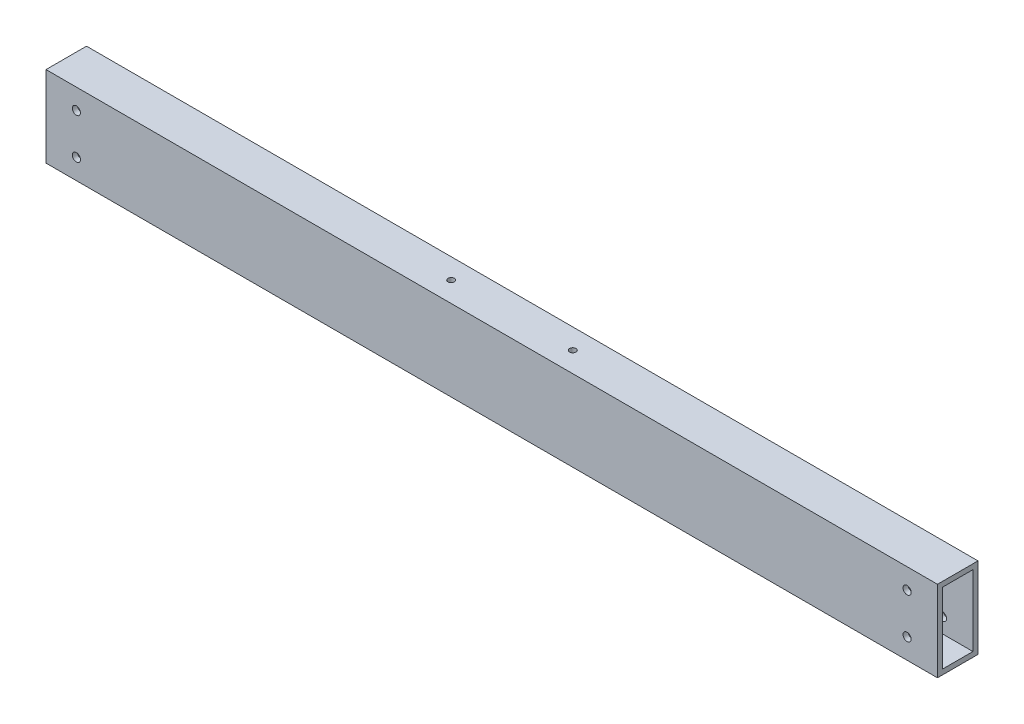
SolidWorks part; units mm, degrees
material "6061-T6 (SS)"
ref_plane "Front Plane" through (0, 0, 0) normal (0, 0, 1) x (1, 0, 0)
ref_plane "Top Plane" through (0, 0, 0) normal (0, 1, 0) x (1, 0, 0)
ref_plane "Right Plane" through (0, 0, 0) normal (1, 0, 0) x (0, 0, -1)
sketch "Sketch1" plane through (0, 0, 0) normal (0, 0, 1) x (1, 0, 0)
  line L1 (-279.4, 25.4) -> (279.4, 25.4)
  line L2 (-279.4, 25.4) -> (-279.4, -25.4)
  line L3 (-279.4, -25.4) -> (279.4, -25.4)
  line L4 (279.4, 25.4) -> (279.4, -25.4)
  line L5 (-279.4, 25.4) -> (279.4, -25.4) construction
  line L6 (-279.4, -25.4) -> (279.4, 25.4) construction
  point P0 (0, 0)
  dimension "D1" = 50.8
  dimension "D2" = 558.8
extrude "Boss-Extrude1" add sketch "Sketch1" along normal mid plane 25.4
sketch "Sketch2" plane through (279.4, 0, 0) normal (1, 0, 0) x (0, 0, -1)
  line L8 (9.525, -22.225) -> (9.525, 22.225)
  line L9 (9.525, 22.225) -> (-9.525, 22.225)
  line L10 (-9.525, 22.225) -> (-9.525, -22.225)
  line L11 (-9.525, -22.225) -> (9.525, -22.225)
  line L12 (9.525, -22.225) -> (9.525, 22.225)
  line L13 (9.525, 22.225) -> (-9.525, 22.225)
  line L14 (-9.525, 22.225) -> (-9.525, -22.225)
  line L15 (-9.525, -22.225) -> (9.525, -22.225)
  dimension "D1" = 3.175
extrude "Cut-Extrude1" cut sketch "Sketch2" against normal through all
sketch "Sketch3" plane through (0, 0, 12.7) normal (0, 0, 1) x (1, 0, 0)
sketch "Sketch4" plane through (0, 25.4, 0) normal (0, 1, 0) x (1, 0, 0)
  line L0 (-279.4, -12.7) -> (-279.4, 12.7) construction
  line L1 (0, -12.7) -> (0, 12.7) construction
  line L2 (279.4, -12.7) -> (-279.4, -12.7) construction
  line L3 (279.4, 12.7) -> (-279.4, 12.7) construction
  circle A0 centre (-304.8, 0) radius 1.7272
  circle A1 centre (-292.1, 0) radius 1.7272
  circle A3 centre (-266.7, 0) radius 1.7272
  circle A4 centre (-254, 0) radius 1.7272
  circle A5 centre (-241.3, 0) radius 1.7272
  circle A7 centre (241.3, 0) radius 1.7272
  circle A8 centre (254, 0) radius 1.7272
  circle A9 centre (266.7, 0) radius 1.7272
  circle A12 centre (-279.4, 0) radius 1.7272 [skipped]
  circle A14 centre (-228.6, 0) radius 1.7272 [skipped]
  dimension "D2" = 3.4544
  dimension "D3" = 7
  dimension "D4" = 12.7
extrude "Cut-Extrude2" [suppressed] cut sketch "Sketch4" against normal blind 6.35
hole_wizard "1/4-20 Tapped Hole1" positions "Sketch8" profile "Sketch7" tap size "1/4-20" standard "ANSI Inch" end condition through all
sketch "Sketch8" plane through (0, 0, 12.7) normal (0, 0, 1) x (1, 0, 0)
  line L0 (-279.4, 25.4) -> (-279.4, -25.4) construction
  line L1 (279.4, -25.4) -> (279.4, 25.4) construction
  line L2 (-279.4, -25.4) -> (279.4, -25.4) construction
  point P0 (-260.35, 12.7)
  point P2 (-260.35, -12.7)
  point P4 (260.35, 12.7)
  point P6 (260.35, -12.7)
  dimension "D1" = 25.4
  dimension "D2" = 19.05
  dimension "D3" = 25.4
  dimension "D4" = 19.05
  dimension "D5" = 12.7
  dimension "D6" = 12.7
sketch "Sketch7" plane through (-260.35, 12.7, 12.7) normal (1, 0, 0) x (0, -1, 0)
  line L0 (0, 0) -> (0, 25.4)
  line L1 (0, 25.4) -> (2.5527, 25.4)
  line L2 (2.5527, 25.4) -> (2.5527, 0)
  line L5 (2.5527, 0) -> (0, 0)
  line L11 (0, -6.35) -> (0, 107.95) construction
  dimension "Thread Major Dia." = 5.1054
  dimension "Thru Tap Drill Depth" = 25.4
hole_wizard "#10-32 Tapped Hole1" positions "Sketch10" profile "Sketch9" tap size "#10-32" standard "ANSI Inch"
sketch "Sketch10" plane through (0, 0, -12.7) normal (0, 0, -1) x (-1, 0, 0)
  line L0 (-279.4, 25.4) -> (279.4, 25.4) construction
  line L1 (-279.4, -25.4) -> (-279.4, 25.4) construction
  point P0 (-190.5, -13.4937)
  point P15 (-114.3, -13.4937)
  point P16 (-38.1, -13.4937)
  point P17 (38.1, -13.4937)
  point P18 (114.3, -13.4937)
  point P19 (190.5, -13.4937)
  dimension "D1" = 76.2
  dimension "D2" = 38.8937
  dimension "D3" = 88.9
  dimension "D5" = 6
sketch "Sketch9" plane through (190.5, -13.4937, -12.7) normal (1, 0, 0) x (0, 1, 0)
  line L0 (0, 0) -> (0, 6.2933)
  line L1 (0, 6.2933) -> (2.0193, 5.08)
  line L2 (2.0193, 5.08) -> (2.0193, 0)
  line L5 (2.0193, 0) -> (0, 0)
  line L10 (0, 6.2933) -> (-2.0193, 5.08) construction
  line L11 (0, -6.35) -> (0, 107.95) construction
  dimension "Tap Drill Dia." = 4.0386
  dimension "Tap Drill Depth" = 5.08
  dimension "Drill Angle" = 118
hole_wizard "5/32 (0.15625) Diameter Hole1" positions "Sketch12" profile "Sketch11" hole size "5/32" standard "ANSI Inch"
sketch "Sketch12" plane through (0, 25.4, 0) normal (0, 1, 0) x (1, 0, 0)
  line L2 (-38.1, 0) -> (38.1, 0) construction
  point P0 (-38.1, 0)
  point P2 (38.1, 0)
  dimension "D1" = 76.2
sketch "Sketch11" plane through (-38.1, 25.4, 0) normal (1, 0, 0) x (0, 0, 1)
  line L0 (0, 0) -> (0, 6.2723)
  line L1 (0, 6.2723) -> (1.9844, 5.08)
  line L2 (1.9844, 5.08) -> (1.9844, 0)
  line L5 (1.9844, 0) -> (0, 0)
  line L10 (0, 6.2723) -> (-1.9844, 5.08) construction
  line L11 (0, -6.35) -> (0, 107.95) construction
  dimension "Hole Dia." = 3.9688
  dimension "Hole Depth" = 5.08
  dimension "Drill Angle" = 118
